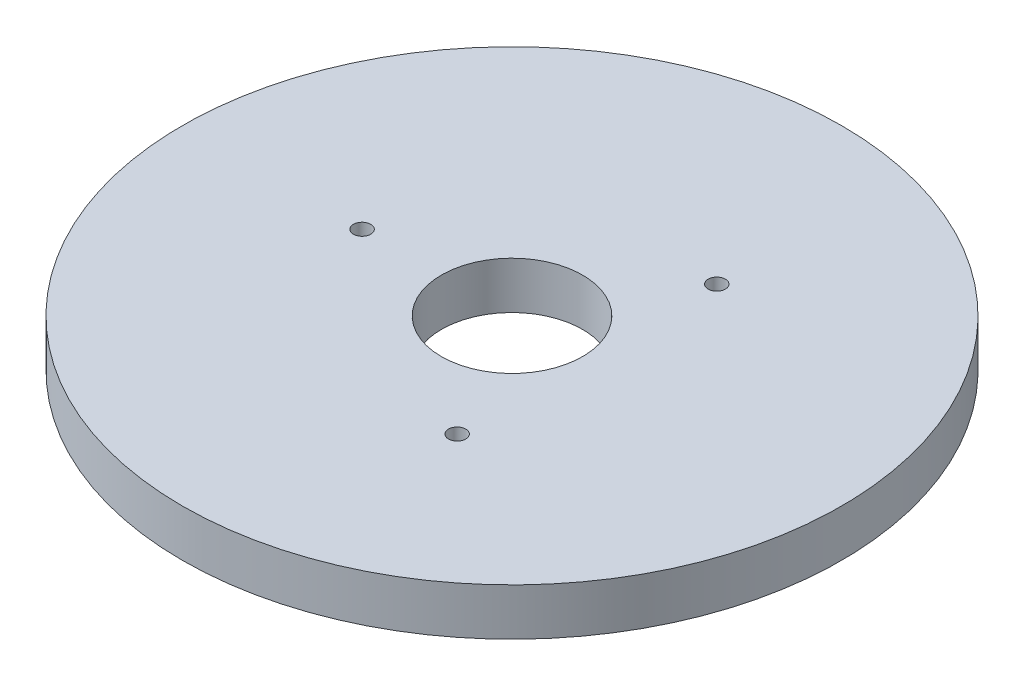
SolidWorks part; units mm, degrees
ref_plane "Front Plane" through (0, 0, 0) normal (0, 0, 1) x (1, 0, 0)
ref_plane "Top Plane" through (0, 0, 0) normal (0, 1, 0) x (1, 0, 0)
ref_plane "Right Plane" through (0, 0, 0) normal (1, 0, 0) x (0, 0, -1)
sketch "Sketch1" plane through (0, 0, 0) normal (0, 1, 0) x (1, 0, 0)
  circle A0 centre (0, 0) radius 70
  dimension "FLANGE_OD" = 140
extrude "Boss-Extrude1" add sketch "Sketch1" along normal blind 10
sketch "Sketch2" plane through (0, 0, 0) normal (0, 1, 0) x (1, 0, 0)
  circle A0 centre (0, 0) radius 15
  dimension "BORE_D" = 30
extrude "Cut-Extrude1" cut sketch "Sketch2" along normal through all
sketch "Sketch3" plane through (0, 10, 0) normal (0, 1, 0) x (1, 0, 0)
  circle A0 centre (0, 0) radius 31.8416 construction
  circle A1 centre (-31.8416, 0) radius 1.8364
  dimension "BOLT_D" = 3.6727
  dimension "BOLT_PCD" = 63.6832
extrude "Cut-Extrude2" cut sketch "Sketch3" against normal blind 6.9794
pattern_circular "CirPattern1" count 3 over 360 about axis through (0, 0, 0) along (0, 1, 0) of "Cut-Extrude2"
